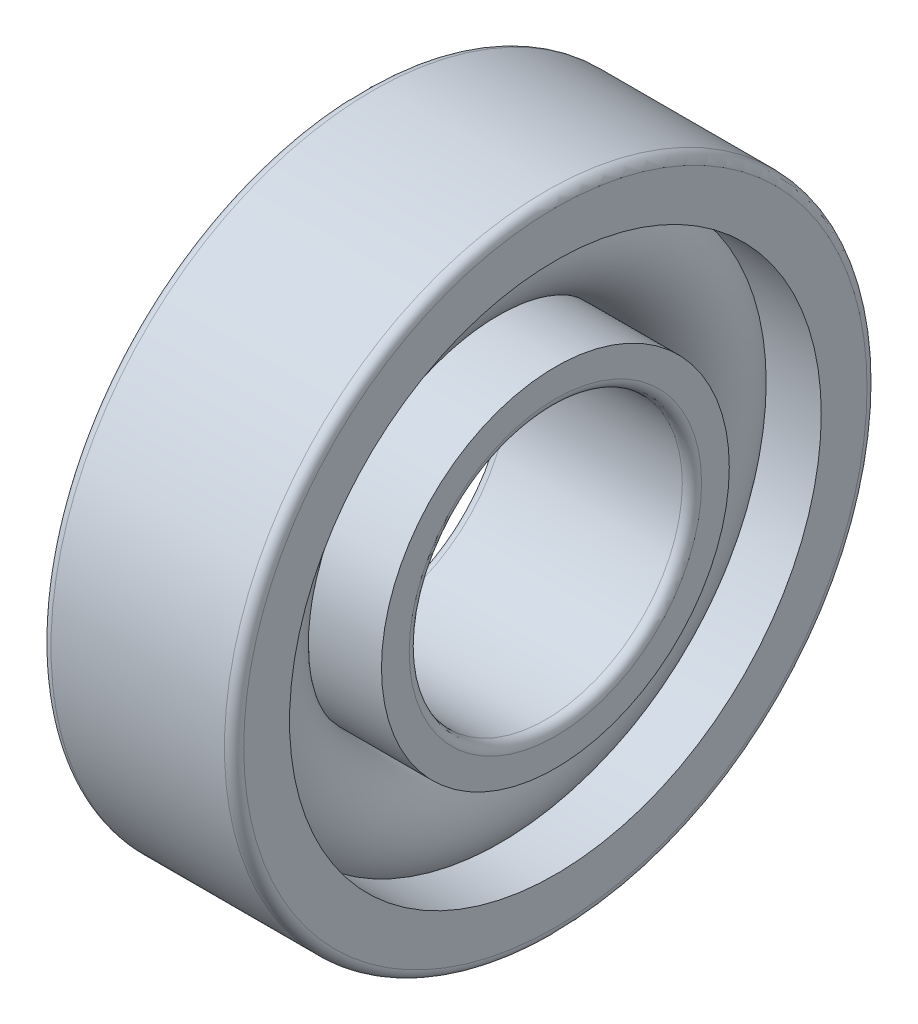
SolidWorks part; units mm, degrees
ref_plane "Plane1" through (0, 0, 0) normal (0, 0, 1) x (1, 0, 0)
ref_plane "Plane2" through (0, 0, 0) normal (0, 1, 0) x (1, 0, 0)
ref_plane "Plane3" through (0, 0, 0) normal (1, 0, 0) x (0, 0, -1)
sketch "Clipboard" plane through (0, 0, 0) normal (0, 0, 1) x (1, 0, 0)
  line L0 (-10, 0) -> (10, 0) construction
  line L1 (0, 0) -> (22.3471, -0.7804)
  line L2 (0, 0) -> (14.2413, 0.4973)
  line L3 (0, 0) -> (22.3471, -0.7804)
  line L4 (0, 0) -> (-22.3573, -0.3902)
  dimension "BallCLRad" = 14.25
  dimension "Count" = 2
  dimension "Show_count" = 2
  dimension "Max_count" = 2
  dimension "Min_count" = 1
sketch "CagSpiSke" plane through (0, 0, 0) normal (0, 0, 1) x (1, 0, 0)
  line L0 (0.8625, 13.675) -> (0.8625, 14.825)
  line L1 (0.8625, 14.825) -> (-0.8625, 14.825)
  line L2 (-0.8625, 14.825) -> (-0.8625, 13.675)
  line L3 (-0.8625, 13.675) -> (0.8625, 13.675)
  line L4 (-20.6375, 0) -> (20.6375, 0) construction
  line L5 (0, 0) -> (0, 23.7692) construction
  dimension "Thickness" = 1.725
  dimension "OD" = 29.65
  dimension "ID" = 27.35
revolve "CageSpine" add sketch "CagSpiSke" angle 0.001 about L4
ref_axis "Axis1" through (-50, 0, 0) along (1, 0, 0)
sketch "CagBalSke" plane through (0, 0, 0) normal (0, 0, 1) x (1, 0, 0)
  line L0 (-3.795, 14.25) -> (3.795, 14.25)
  line L1 (-1.905, 14.25) -> (1.905, 14.25) construction
  line L2 (-10, 0) -> (10, 0) construction
  line L3 (0, 0) -> (0, 24) construction
  arc A0 (3.795, 14.25) -> (-3.795, 14.25) centre (0, 14.25) cw
  dimension "CageWallOD" = 7.59
  dimension "BallCLRad" = 14.25
revolve "CageBall" [suppressed] add sketch "CagBalSke" angle 360 about L1 reverse direction yes
pattern_circular "CageBalls" [suppressed] count 2 every 180 about axis through (-50, 0, 0) along (1, 0, 0)
sketch "CagTrmODSke" plane through (0, 0, 0) normal (0, 0, 1) x (1, 0, 0)
  line L0 (3.796, 14.825) -> (3.796, 18.046)
  line L1 (3.796, 18.046) -> (-3.796, 18.046)
  line L2 (-3.796, 18.046) -> (-3.796, 14.825)
  line L3 (-3.796, 14.825) -> (3.796, 14.825)
  line L4 (-20.6375, 0) -> (20.6375, 0) construction
  line L5 (0, 0) -> (0, 25) construction
  dimension "Width" = 7.592
  dimension "ID" = 29.65
  dimension "OD" = 36.092
revolve "CageTrimOD" [suppressed] cut sketch "CagTrmODSke" angle 360 about L4 reverse direction yes
sketch "CagTrmIDSke" plane through (0, 0, 0) normal (0, 0, 1) x (1, 0, 0)
  line L0 (3.796, 10.456) -> (3.796, 13.675)
  line L1 (3.796, 13.675) -> (-3.796, 13.675)
  line L2 (-3.796, 13.675) -> (-3.796, 10.456)
  line L3 (-3.796, 10.456) -> (3.796, 10.456)
  line L4 (-20.6375, 0) -> (20.6375, 0) construction
  line L5 (0, 0) -> (0, 25) construction
  dimension "ID" = 20.912
  dimension "OD" = 27.35
  dimension "Width" = 7.592
revolve "CageTrimID" [suppressed] cut sketch "CagTrmIDSke" angle 360 about L4 reverse direction yes
sketch "BalSimSke" plane through (0, 0, 0) normal (0, 0, 1) x (1, 0, 0)
  line L0 (-10, 0) -> (10, 0) construction
  line L1 (-10, 14.25) -> (10, 14.25) construction
  line L2 (0, 0) -> (0, 23) construction
  circle A0 centre (0, 14.25) radius 3.45
  dimension "Ball_diameter" = 6.9
  dimension "BallCLRad" = 14.25
revolve "BallsSimplified" add sketch "BalSimSke" angle 360 about L0
sketch "BalDetSke" plane through (0, 0, 0) normal (0, 0, 1) x (1, 0, 0)
  line L0 (-3.45, 14.25) -> (3.45, 14.25)
  line L1 (-1.905, 14.25) -> (1.905, 14.25) construction
  line L2 (0, 0) -> (0, 25) construction
  arc A0 (3.45, 14.25) -> (-3.45, 14.25) centre (0, 14.25) cw
  dimension "Ball_diameter" = 6.9
  dimension "BallCLRad" = 14.25
revolve "BallDetailed" [suppressed] add sketch "BalDetSke" angle 360 about L1 reverse direction yes
sketch "InnRacSke" plane through (0, 0, 0) normal (0, 0, 1) x (1, 0, 0)
  line L0 (-2.5378, 11.95) -> (-6, 11.95)
  line L1 (-6, 11.95) -> (-6, 9.1)
  line L2 (-5.4, 8.5) -> (5.4, 8.5)
  line L3 (6, 9.1) -> (6, 10.825)
  line L4 (0, 10.825) -> (6, 10.825)
  line L5 (-20.6375, 0) -> (20.6375, 0) construction
  line L6 (0, 0) -> (0, 30) construction
  arc A0 (-6, 9.1) -> (-5.4, 8.5) centre (-5.4, 9.1) ccw
  arc A1 (5.4, 8.5) -> (6, 9.1) centre (5.4, 9.1) ccw
  arc A2 (0, 10.825) -> (-2.5378, 11.95) centre (0, 14.25) cw
  dimension "Fillet_radius" = 0.6
  dimension "Ball_diameter" = 6.85
  dimension "ID" = 17
  dimension "OD" = 23.9
  dimension "Width" = 12
  dimension "BallCLRad" = 14.25
revolve "InnerRace" add sketch "InnRacSke" angle 360 about L5 reverse direction yes
sketch "OutRacSke" plane through (0, 0, 0) normal (0, 0, 1) x (1, 0, 0)
  line L0 (0, 17.675) -> (-6, 17.675)
  line L1 (-6, 17.675) -> (-6, 19.4)
  line L2 (-5.4, 20) -> (5.4, 20)
  line L3 (6, 19.4) -> (6, 16.55)
  line L4 (6, 16.55) -> (2.5378, 16.55)
  line L5 (-20.6375, 0) -> (20.6375, 0) construction
  line L6 (0, 0) -> (0, 30) construction
  arc A0 (-6, 19.4) -> (-5.4, 20) centre (-5.4, 19.4) cw
  arc A1 (5.4, 20) -> (6, 19.4) centre (5.4, 19.4) cw
  arc A2 (2.5378, 16.55) -> (0, 17.675) centre (0, 14.25) ccw
  dimension "Fillet_radius" = 0.6
  dimension "Ball_diameter" = 6.85
  dimension "OD" = 40
  dimension "ID" = 33.1
  dimension "Width" = 12
  dimension "BallCLRad" = 14.25
revolve "OuterRace" add sketch "OutRacSke" angle 360 about L5 reverse direction yes
pattern_circular "BallsDetailed" [suppressed] count 2 every 180 about axis through (-50, 0, 0) along (1, 0, 0)
equation "\"BallCLRad@Clipboard\" = ( \"OD@OutRacSke\" + \"ID@InnRacSke\" ) / 4"
equation "\"BallCLRad@BalSimSke\" = \"BallCLRad@Clipboard\""
equation "\"BallCLRad@BalDetSke\" = \"BallCLRad@Clipboard\""
equation "\"BallCLRad@InnRacSke\" = \"BallCLRad@Clipboard\""
equation "\"BallCLRad@OutRacSke\" = \"BallCLRad@Clipboard\""
equation "\"Ball_diameter@InnRacSke\" = \"Ball_diameter@BalDetSke\" - 0.05"
equation "\"Ball_diameter@OutRacSke\" = \"Ball_diameter@BalDetSke\" - 0.05"
equation "\"Ball_diameter@BalSimSke\" = \"Ball_diameter@BalDetSke\""
equation "\"Width@OutRacSke\" = \"Width@InnRacSke\""
equation "\"Fillet_radius@OutRacSke\" = \"Fillet_radius@InnRacSke\""
equation "\"Max_count@Clipboard\" = int( 3.14159265 / atn(( \"Ball_diameter@BalDetSke\" / 2) / sqr( \"BallCLRad@Clipboard\"  *  \"BallCLRad@Clipboard\" - ( \"Ball_diameter@BalDetSke\" / 2) *  ( \"Ball_diameter@BalDetSke\" / 2))))"
equation "\"Max_count@Clipboard\" = ((sgn( \"Max_count@Clipboard\" - \"Count@Clipboard\" )-1)*( \"Max_count@Clipboard\" - \"Count@Clipboard\" ))/-2+ \"Count@Clipboard\""
equation "\"Count@BallsDetailed\" = int( \"Show_count@Clipboard\" ) "
equation "\"Count@BallsDetailed\" = ((sgn( \"Count@BallsDetailed\" - \"Max_count@Clipboard\" )-1)*( \"Count@BallsDetailed\" - \"Max_count@Clipboard\" ))/-2+ \"Max_count@Clipboard\""
equation "\"Count@BallsDetailed\" = ((sgn( \"Count@BallsDetailed\" - \"Min_count@Clipboard\" )+1)*( \"Count@BallsDetailed\" - \"Min_count@Clipboard\"))/2 +\"Min_count@Clipboard\""
equation "\"Angle@BallsDetailed\" = 360.0 / \"Max_count@Clipboard\""
equation "\"BallCLRad@CagBalSke\" = \"BallCLRad@Clipboard\""
equation "\"Count@CageBalls\" = \"Count@BallsDetailed\""
equation "\"Angle@CageBalls\" = \"Angle@BallsDetailed\""
equation "\"Angle@CageSpine\" =  \"Angle@CageBalls\" * ( \"Count@CageBalls\" -1 + int( \"Count@CageBalls\" / \"Max_count@Clipboard\" ) )  + 0.001 -  int( \"Count@CageBalls\" / \"Max_count@Clipboard\" ) * 0.001"
equation "\"Angle@CageSpine\" =  \"Angle@CageSpine\" * int( \"Min_count@Clipboard\" / 2) + int(1 / \"Min_count@Clipboard\")  * 0.001"
equation "\"CageWallOD@CagBalSke\" =  \"Ball_diameter@BalDetSke\" * 1.1"
equation "\"Thickness@CagSpiSke\" =  \"Ball_diameter@BalDetSke\" * 0.25"
equation "\"OD@CagTrmODSke\" = \"BallCLRad@Clipboard\" * 2 + \"CageWallOD@CagBalSke\" + 0.002"
equation "\"ID@CagTrmODSke\" = \"BallCLRad@Clipboard\" * 2 + \"Ball_diameter@BalDetSke\" / 6"
equation "\"OD@CagTrmIDSke\" = \"BallCLRad@Clipboard\" * 2 - \"Ball_diameter@BalDetSke\" / 6"
equation "\"ID@CagTrmIDSke\" = \"BallCLRad@Clipboard\" * 2 - \"CageWallOD@CagBalSke\" + 0.002"
equation "\"OD@CagSpiSke\" = \"ID@CagTrmODSke\""
equation "\"ID@CagSpiSke\" = \"OD@CagTrmIDSke\""
equation "\"Width@CagTrmODSke\" = \"CageWallOD@CagBalSke\" + 0.002"
equation "\"Width@CagTrmIDSke\" = \"CageWallOD@CagBalSke\" + 0.002"
